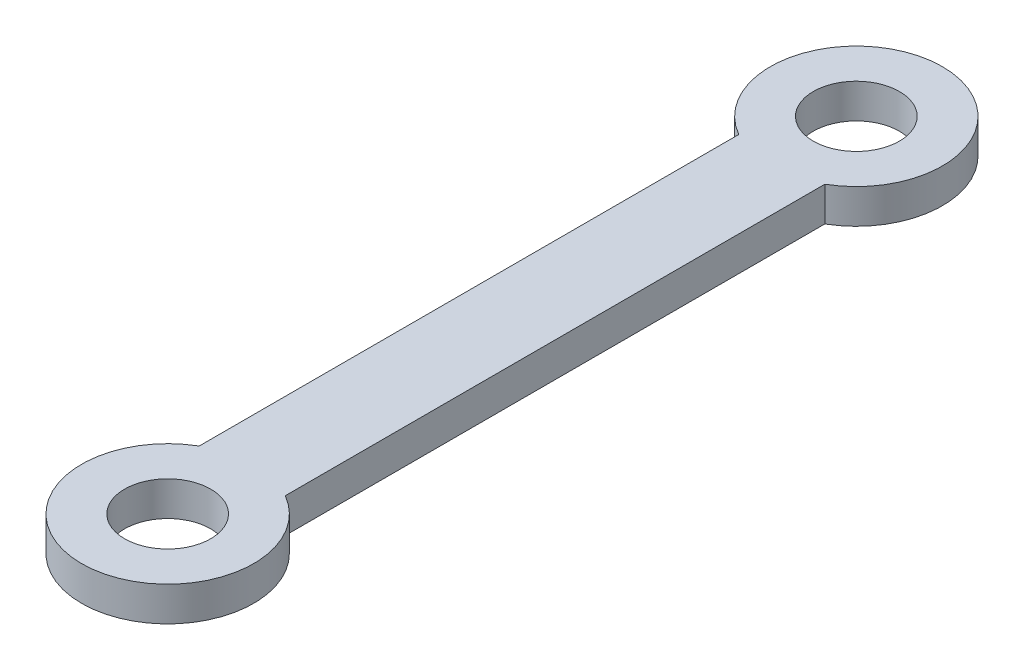
SolidWorks part; units mm, degrees
ref_plane "Front Plane" through (0, 0, 0) normal (0, 0, 1) x (1, 0, 0)
ref_plane "Top Plane" through (0, 0, 0) normal (0, 1, 0) x (1, 0, 0)
ref_plane "Right Plane" through (0, 0, 0) normal (1, 0, 0) x (0, 0, -1)
sketch "Sketch1" plane through (0, 0, 0) normal (0, 1, 0) x (1, 0, 0)
  line L0 (-3.175, 45.3007) -> (-3.175, 5.4993)
  line L1 (3.175, 45.3007) -> (3.175, 5.4993)
  circle A0 centre (0, 0) radius 3.175
  arc A1 (-3.175, 5.4993) -> (3.175, 5.4993) centre (0, 0) ccw
  circle A4 centre (0, 50.8) radius 3.175
  arc A5 (3.175, 45.3007) -> (-3.175, 45.3007) centre (0, 50.8) ccw
  dimension "D2" = 12.7
  dimension "D3" = 6.35
  dimension "D1" = 50.8
  dimension "D4" = 6.35
extrude "Boss-Extrude1" add sketch "Sketch1" along normal blind 2.54
